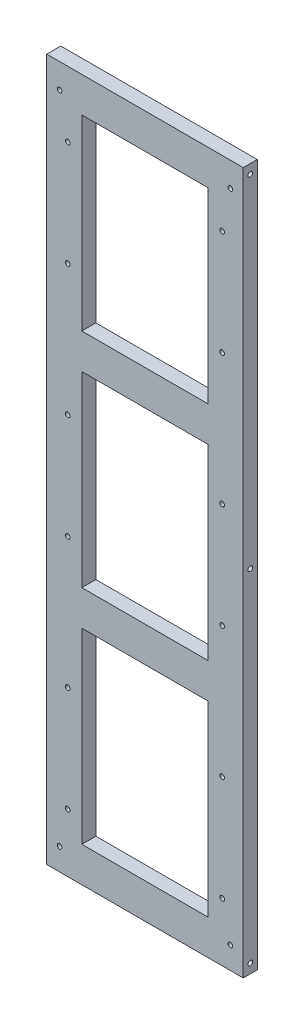
SolidWorks part; units mm, degrees
material "Alumina"
ref_plane "Front Plane" through (0, 0, 0) normal (0, 0, 1) x (1, 0, 0)
ref_plane "Top Plane" through (0, 0, 0) normal (0, 1, 0) x (1, 0, 0)
ref_plane "Right Plane" through (0, 0, 0) normal (1, 0, 0) x (0, 0, -1)
sketch "Sketch1" plane through (0, 0, 0) normal (0, 0, 1) x (1, 0, 0)
  line L0 (27, 135) -> (27, 55)
  line L9 (-42, -150) -> (42, -150)
  line L10 (-42, -150) -> (-42, 150)
  line L11 (-42, 150) -> (42, 150)
  line L12 (42, -150) -> (42, 150)
  line L13 (0, 0) -> (0, 40) construction
  line L15 (-27, -135) -> (27, -135)
  line L16 (-27, -135) -> (-27, -55)
  line L17 (-27, 135) -> (27, 135)
  line L21 (-27, 55) -> (27, 55)
  line L23 (-27, 40) -> (27, 40)
  line L25 (-27, -40) -> (27, -40)
  line L27 (-27, -55) -> (27, -55)
  line L33 (27, 40) -> (27, -40)
  line L34 (-27, 55) -> (-27, 135)
  line L35 (-27, -40) -> (-27, 40)
  line L36 (27, -55) -> (27, -135)
  dimension "D1" = 84
  dimension "D2" = 300
  dimension "D3" = 54
  dimension "D4" = 270
  dimension "D5" = 15
  dimension "D6" = 80
  dimension "D7" = 15
  dimension "D8" = 80
  dimension "D9" = 15
  dimension "D10" = 15
  dimension "D11" = 80
  dimension "D12" = 40
  dimension "D13" = 15
extrude "Boss-Extrude1" add sketch "Sketch1" along normal blind 6
sketch "Sketch2" plane through (42, 0, 0) normal (1, 0, 0) x (0, 0, -1)
  line L0 (-6, 150) -> (0, 150) construction
  line L1 (-6, -150) -> (-6, 150) construction
  line L3 (-3, 146) -> (-3, 0) construction
  circle A0 centre (-3, 146) radius 1
  circle A4 centre (-3, 0) radius 1
  circle A5 centre (-3, -146) radius 1
  circle A6 centre (-3, -292) radius 1
  dimension "D1" = 4
  dimension "D3" = 2
  dimension "D4" = 3
  dimension "D2" = 4
  dimension "D5" = 146
extrude "Cut-Extrude1" cut sketch "Sketch2" against normal blind 10
mirror "Mirror1" about plane through (0, 0, 0) normal (1, 0, 0) of "Cut-Extrude1"
sketch "Sketch4" plane through (0, 0, 6) normal (0, 0, 1) x (1, 0, 0)
  line L0 (-42, -150) -> (-42, 150) construction
  line L2 (-42, 150) -> (42, 150) construction
  line L4 (-42, -150) -> (42, -150) construction
  line L8 (-33, 122) -> (-33, -125) construction
  line L9 (0, -3.3) -> (0, 3.3) construction
  line L10 (33, 122) -> (33, -125) construction
  circle A8 centre (-33, 122) radius 1
  circle A40 centre (-33, -125) radius 1
  circle A41 centre (-33, 77) radius 1
  circle A42 centre (-33, -80) radius 1
  circle A43 centre (-33, 21) radius 1
  circle A44 centre (-33, -24) radius 1
  circle A45 centre (33, -24) radius 1
  circle A46 centre (33, 21) radius 1
  circle A47 centre (33, -80) radius 1
  circle A48 centre (33, 77) radius 1
  circle A49 centre (33, -125) radius 1
  circle A53 centre (33, 122) radius 1
  dimension "D7" = 2
  dimension "D6" = 25
  dimension "D14" = 2
  dimension "D16" = 2
  dimension "D19" = 45
  dimension "D20" = 2
  dimension "D22" = 2
  dimension "D23" = 2
  dimension "D24" = 45
  dimension "D25" = 56
  dimension "D21" = 56
  dimension "D5" = 28
  dimension "D9" = 9
extrude "Cut-Extrude3" cut sketch "Sketch4" against normal blind 10
sketch "Sketch5" plane through (0, 0, 6) normal (0, 0, 1) x (1, 0, 0)
  line L0 (-36.5, 139.5) -> (36.5, 139.5) construction
  line L1 (36.5, 139.5) -> (36.5, -140.5) construction
  line L2 (36.5, -140.5) -> (-36.5, -140.5) construction
  line L3 (-36.5, -140.5) -> (-36.5, 139.5) construction
  line L4 (-42, 150) -> (-42, -150) construction
  line L5 (42, 150) -> (-42, 150) construction
  line L6 (42, -150) -> (42, 150) construction
  line L7 (-42, -150) -> (42, -150) construction
  circle A0 centre (-36.5, -140.5) radius 1
  circle A1 centre (36.5, -140.5) radius 1
  circle A2 centre (-36.5, 139.5) radius 1
  circle A3 centre (36.5, 139.5) radius 1
  dimension "D5" = 2
  dimension "D6" = 2
  dimension "D7" = 2
  dimension "D8" = 2
  dimension "D1" = 5.5
  dimension "D2" = 10.5
  dimension "D3" = 5.5
  dimension "D4" = 9.5
extrude "Cut-Extrude4" cut sketch "Sketch5" against normal blind 10
